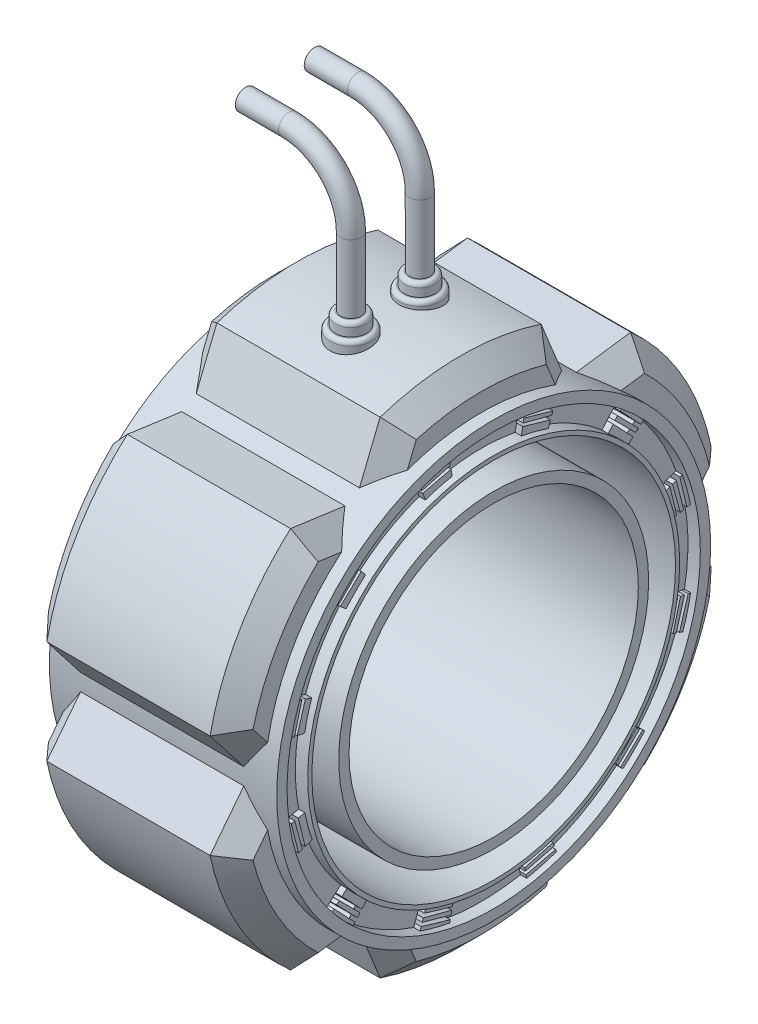
SolidWorks part; units mm, degrees
ref_plane "Front Plane" through (0, 0, 0) normal (0, 0, 1) x (1, 0, 0)
ref_plane "Top Plane" through (0, 0, 0) normal (0, 1, 0) x (1, 0, 0)
ref_plane "Right Plane" through (0, 0, 0) normal (1, 0, 0) x (0, 0, -1)
sketch "Sketch6" plane through (0, 0, 0) normal (1, 0, 0) x (0, 0, -1)
  circle A0 centre (0, 0) radius 75
  circle A1 centre (0, 0) radius 80
  circle A2 centre (0, 0) radius 100
  circle A3 centre (0, 0) radius 90
  dimension "D1" = 150
  dimension "D2" = 160
  dimension "D3" = 180
  dimension "D4" = 200
extrude "Extrude-Thin1" add sketch "Sketch6" along normal blind 110 separate body thin contours A2 thin type one direction wall 5
extrude "Extrude-Thin2" add sketch "Sketch6<5>" along normal blind 110 separate body thin contours A0 thin type one direction reverse wall 5
sketch "Sketch6<5>" plane through (0, 0, 0) normal (1, 0, 0) x (0, 0, -1) same geometry as "Sketch6"
extrude "Extrude-Thin3" add sketch "Sketch6<6>" along normal blind 110 separate body thin contours A3 thin type one direction reverse wall 2
sketch "Sketch6<6>" plane through (0, 0, 0) normal (1, 0, 0) x (0, 0, -1) same geometry as "Sketch6"
ref_plane "Plane1" through (60, 0, 0) normal (1, 0, 0) x (0, 0, -1)
sketch "Sketch8" plane through (60, 0, 0) normal (1, 0, 0) x (0, 0, -1)
  line L0 (-18.9452, 98.189) -> (-17.0507, 88.3701)
  line L1 (18.2163, 98.3268) -> (16.3946, 88.4942)
  circle A0 centre (0, 0) radius 90 construction
  circle A1 centre (0, 0) radius 100 construction
  arc A2 (16.3946, 88.4942) -> (-17.0507, 88.3701) centre (0, 0) ccw
  arc A3 (18.2163, 98.3268) -> (-18.9452, 98.189) centre (0, 0) ccw
extrude "Boss-Extrude1" add sketch "Sketch8" along normal blind 44 and the other way blind 52
pattern_circular "CirPattern1" count 12 over 360 about axis through (0, 0, 0) along (1, 0, 0) of "Boss-Extrude1"
sketch "Sketch9" plane through (60, 0, 0) normal (1, 0, 0) x (0, 0, -1)
  line L0 (18.2163, 98.3268) -> (16.3946, 88.4942)
  line L2 (32.6875, 94.5068) -> (29.4187, 85.0561)
  line L3 (32.6875, 94.5068) -> (29.4187, 85.0561) construction
  line L4 (16.7304, 90.3066) -> (29.9057, 86.4641)
  line L5 (17.9883, 97.0963) -> (32.1298, 92.8943)
  line L6 (17.3054, 93.4105) -> (31.0531, 89.7814)
  line L7 (17.0613, 92.0927) -> (30.4834, 88.1341)
  line L8 (17.6617, 95.3337) -> (31.6035, 91.3728)
  circle A0 centre (0, 0) radius 90 construction
  circle A1 centre (0, 0) radius 100 construction
  arc A2 (29.4187, 85.0561) -> (16.3946, 88.4942) centre (0, 0) ccw
  arc A3 (32.6875, 94.5068) -> (18.2163, 98.3268) centre (0, 0) ccw
  point P12 (31.0531, 89.7814)
extrude "Boss-Extrude2" add sketch "Sketch9" along normal blind 47 and the other way blind 55 contours L2 A3 L0 L5 | A2 L2 L4 L0 | L8 L0 L6 L2 | L7 L0 L4 L2 region at (60, 95.7086, -25.6088) region at (60, 92.5242, -24.2359) region at (60, 89.2598, -23.5199) region at (60, 87.7327, -22.8781)
pattern_circular "CirPattern2" count 12 over 360 about axis through (110, 0, 0) along (1, 0, 0) of "Boss-Extrude2"
sketch "Sketch10" plane through (60, 0, 0) normal (1, 0, 0) x (0, 0, -1)
  line L0 (-38.9598, 117.5196) -> (-48.9573, 92.888)
  line L1 (0, 0) -> (0, 39.2096) construction
  line L2 (38.9598, 117.5196) -> (48.9573, 92.888)
  arc A0 (38.9598, 117.5196) -> (-38.9598, 117.5196) centre (0, 0) ccw
  circle A1 centre (0, 0) radius 105 construction
  arc A2 (48.9573, 92.888) -> (-48.9573, 92.888) centre (0, 0) ccw
extrude "Boss-Extrude3" add sketch "Sketch10" along normal blind 44 and the other way blind 55
chamfer "Chamfer1" distance 10 angle 45 6 edges at (5, 105.2038, 43.9585) (5, 123.8092, 0) (5, 105.2038, -43.9585) (104, 105.2038, -43.9585) (104, 123.8092, 0) (104, 105.2038, 43.9585)
pattern_circular "CirPattern3" count 6 over 360 about axis through (110, 0, 0) along (1, 0, 0) of "Chamfer1", "Boss-Extrude3"
sketch3d "3DSketch1"
  line L0 (57.5936, 102.0171, 16.6744) -> (57.5936, 166.0031, 16.6744)
  line L1 (27.5936, 196.0031, 16.6744) -> (6.6387, 196.0031, 16.6744)
  arc A0 (27.5936, 196.0031, 16.6744) -> (57.5936, 166.0031, 16.6744) centre (27.5936, 166.0031, 16.6744) ccw
  point P6 (11.6326, 187.2758, -14.9462)
  point P7 (69.8954, 102.0171, 20.9719)
  point P8 (57.5936, 102.0171, 16.6744)
  point P9 (58.7011, 93.9017, -15.308)
  point P10 (0, 0, 0)
  point P11 (0, 0, 0)
  point P14 (57.5936, 196.0031, 16.6744)
  point P15 (27.5936, 166.0031, -13.3256)
  point P24 (59.8629, 104.1113, -14.7648)
  dimension "D1" = 30
sweep "Sweep1" add path "3DSketch1" circular profile diameter 10 parameters "D3"=10
mirror "Mirror1" about plane through (0, 0, 0) normal (0, 0, 1) of "Sweep1"
ref_plane "Plane2" through (0, 120, 0) normal (0, 1, 0) x (1, 0, 0)
sketch "Sketch21" plane through (0, 120, 0) normal (0, 1, 0) x (1, 0, 0)
  circle A0 centre (57.5936, 16.6744) radius 10
  circle A1 centre (57.5936, 16.6744) radius 7.5
  dimension "D1" = 20
  dimension "D2" = 15
extrude "Boss-Extrude4" add sketch "Sketch21" along normal blind 7 and the other way blind 1 contours A0 A1 | A1 region at (47.8764, 120, -16.6744)
extrude "Boss-Extrude5" add sketch "Sketch21<3>" along normal blind 13 contours A1 region at (57.5936, 120, -16.6744)
sketch "Sketch21<3>" plane through (0, 120, 0) normal (0, 1, 0) x (1, 0, 0) same geometry as "Sketch21"
fillet "Fillet1" radius 2 2 edges at (57.5936, 127, -6.6744) (57.5936, 133, -9.1744)
mirror "Mirror2" about plane through (0, 0, 0) normal (0, 0, 1) of "Fillet1", "Boss-Extrude5", "Boss-Extrude4"
